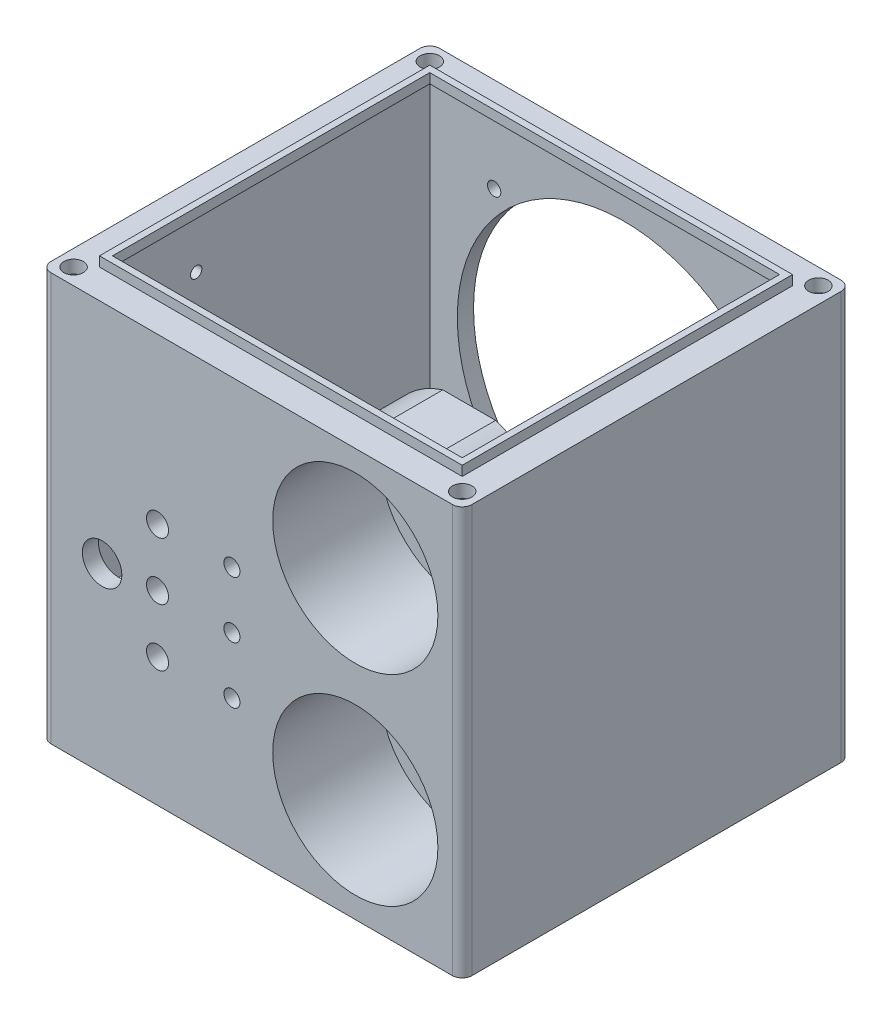
SolidWorks part; units mm, degrees
ref_plane "Front Plane" through (0, 0, 0) normal (0, 0, 1) x (1, 0, 0)
ref_plane "Top Plane" through (0, 0, 0) normal (0, 1, 0) x (1, 0, 0)
ref_plane "Right Plane" through (0, 0, 0) normal (1, 0, 0) x (0, 0, -1)
sketch "Sketch1" plane through (0, 0, 0) normal (0, 0, 1) x (1, 0, 0)
  line L1 (65, -63) -> (-65, -63)
  line L2 (65, -63) -> (65, 63)
  line L3 (65, 63) -> (-65, 63)
  line L4 (-65, -63) -> (-65, 63)
  line L5 (65, -63) -> (-65, 63) construction
  line L6 (65, 63) -> (-65, -63) construction
  point P0 (0, 0)
  dimension "D1" = 126
  dimension "D2" = 130
extrude "Boss-Extrude1" add sketch "Sketch1" along normal blind 120
sketch "Sketch2" plane through (0, 0, 120) normal (0, 0, 1) x (1, 0, 0)
  line L0 (32, 63) -> (32, 31) construction
  line L1 (3.05, -33) -> (-58, -33) construction
  line L2 (3.05, -33) -> (3.05, 21.94) construction
  line L3 (3.05, 21.94) -> (-58, 21.94) construction
  line L4 (-58, -33) -> (-58, 21.94) construction
  line L5 (3.05, -33) -> (-58, 21.94) construction
  line L6 (3.05, 21.94) -> (-58, -33) construction
  line L7 (65, 63) -> (-65, 63) construction
  line L8 (32, 0) -> (32, 31) construction
  line L9 (32, 31) -> (65, 31) construction
  line L10 (65, -63) -> (65, 63) construction
  line L11 (65, 31) -> (32, 0) construction
  line L12 (-47.475, -63) -> (-47.475, -53) construction
  line L13 (-65, -63) -> (65, -63) construction
  line L14 (-47.475, -53) -> (-7.475, -53) construction
  line L15 (-7.475, -53) -> (-7.475, -63) construction
  line L16 (-7.475, -63) -> (-47.475, -63) construction
  line L17 (32, 0) -> (65, 0) construction
  line L18 (-65, 63) -> (-65, -63) construction
  line L19 (-27.475, -5.53) -> (-27.475, -53) construction
  line L20 (-29.08, 12.19) -> (-6.1, 12.19) construction
  line L21 (32, -63.385) -> (65, -63.385) construction
  line L22 (-6.1, 12.19) -> (-6.1, -5.31) construction
  line L23 (32, 63.385) -> (65, 63.385) construction
  line L24 (-6.1, -5.31) -> (-6.1, -22.81) construction
  line L26 (-29.08, -23.31) -> (-29.08, -5.56) construction
  line L27 (-29.08, -5.56) -> (-29.08, 12.19) construction
  line L29 (-46.2, -6.9) -> (-46.2, -5.56) construction
  line L30 (-46.2, -5.56) -> (-29.08, -5.56) construction
  circle A0 centre (32, 31) radius 11
  circle A1 centre (-47.475, -53) radius 6 construction
  circle A2 centre (-7.475, -53) radius 6 construction
  circle A3 centre (32, 49.7) radius 3.55
  circle A4 centre (32, 31) radius 32.385 construction
  circle A5 centre (32, -31) radius 32.385 construction
  circle A6 centre (32, 31) radius 18.7 construction
  circle A7 centre (-46.2, -6.9) radius 6.1
  circle A8 centre (-29.08, -5.56) radius 3.4
  circle A9 centre (-29.08, 12.19) radius 3.4
  circle A10 centre (-29.08, -23.31) radius 3.4
  circle A11 centre (-6.1, -22.81) radius 2.476
  circle A12 centre (-6.1, -5.31) radius 2.476
  circle A13 centre (-6.1, 12.19) radius 2.476
  circle A14 centre (32, -49.7) radius 3.55
  circle A15 centre (32, -31) radius 18.7 construction
  circle A16 centre (32, 12.3) radius 3.55
  circle A17 centre (32, -31) radius 11
  circle A18 centre (32, -12.3) radius 3.55
  circle A19 centre (32, 31) radius 18.465 construction
  circle A20 centre (32, -31) radius 18.465 construction
  point P0 (-27.475, -5.53)
  dimension "D1" = 64.77
  dimension "D2" = 61.05
  dimension "D7" = 12
  dimension "D12" = 22
  dimension "D13" = 7.1
  dimension "D14" = 4.952
  dimension "D15" = 6.8
  dimension "D20" = 12.2
  dimension "D24" = 37.4
  dimension "D9" = 36.93
  dimension "D3" = 54.94
  dimension "D4" = 7
  dimension "D5" = 40
  dimension "D6" = 31
  dimension "D8" = 20
  dimension "D10" = 33
  dimension "D11" = 30
  dimension "D16" = 17.75
  dimension "D17" = 17.5
  dimension "D18" = 1.34
  dimension "D19" = 17.12
  dimension "D21" = 11.8
  dimension "D22" = 22.98
  dimension "D23" = 9.69
sketch "Sketch3" plane through (0, 63, 0) normal (0, 1, 0) x (1, 0, 0)
  line L1 (65, -120) -> (-65, -120) construction
  line L2 (65, -120) -> (65, 0) construction
  line L3 (65, 0) -> (-65, 0) construction
  line L4 (-65, -120) -> (-65, 0) construction
  line L5 (65, -120) -> (-65, 0) construction
  line L6 (65, 0) -> (-65, -120) construction
  line L7 (60, -115) -> (-60, -115)
  line L8 (60, -115) -> (60, -5)
  line L9 (60, -5) -> (-60, -5)
  line L10 (-60, -115) -> (-60, -5)
  line L11 (60, -115) -> (-60, -5) construction
  line L12 (60, -5) -> (-60, -115) construction
  point P0 (0, -60)
  point P6 (0, -60)
  dimension "D1" = 5
  dimension "D2" = 5
extrude "Cut-Extrude3" cut sketch "Sketch3" against normal blind 121
extrude "Cut-Extrude4" cut sketch "Sketch2" against normal up to surface (5 mm away) up to face at (0, 2.5, 115)
sketch "Sketch6" plane through (0, 0, 0) normal (0, 0, -1) x (-1, 0, 0)
  line L0 (0, -1.25) -> (0, -63) construction
  line L1 (0, -1.25) -> (-40.1283, 38.8783) construction
  line L2 (-40.1283, 38.8783) -> (40.1283, 38.8783) construction
  line L3 (40.1283, 38.8783) -> (40.1283, -41.3783) construction
  line L4 (40.1283, -41.3783) -> (-40.1283, -41.3783) construction
  line L5 (-40.1283, -41.3783) -> (-40.1283, 38.8783) construction
  line L7 (65, -63) -> (-65, -63) construction
  line L8 (0, -58) -> (65, -58) construction
  line L9 (65, 63) -> (65, -63) construction
  line L10 (65, -58) -> (0, -1.25) construction
  line L11 (0, -1.25) -> (56.75, -1.25) construction
  line L12 (56.75, -1.25) -> (65, -1.25) construction
  circle A0 centre (0, -1.25) radius 51.5
  circle A1 centre (0, -1.25) radius 56.75 construction
  circle A2 centre (40.1283, -41.3783) radius 2.05
  circle A3 centre (-40.1283, -41.3783) radius 2.05
  circle A4 centre (40.1283, 38.8783) radius 2.05
  circle A5 centre (-40.1283, 38.8783) radius 2.05
  dimension "D2" = 103
  dimension "D3" = 113.5
  dimension "D4" = 4.1
  dimension "D1" = 5
  dimension "D5" = 135
extrude "Cut-Extrude5" cut sketch "Sketch6" against normal up to surface (5 mm away) up to face at (0, 2.5, 5)
sketch "Sketch7" plane through (0, 63, 0) normal (0, 1, 0) x (1, 0, 0)
  line L0 (60, -115) -> (60, -5) construction
  line L1 (-60, -5) -> (60, -5)
  line L2 (-60, -5) -> (-60, -115)
  line L3 (-60, -115) -> (60, -115)
  line L4 (60, -5) -> (60, -115)
  line L5 (-65, -120) -> (-65, 0) construction
  line L6 (54, -109) -> (-54, -109)
  line L7 (54, -109) -> (54, -11)
  line L8 (54, -11) -> (-54, -11)
  line L9 (-54, -109) -> (-54, -11)
  line L10 (54, -109) -> (-54, -11) construction
  line L11 (54, -11) -> (-54, -109) construction
  line L12 (65, 0) -> (-65, 0) construction
  line L13 (-60, -60) -> (60, -60) construction
  line L15 (0, 0) -> (0, -120) construction
  line L16 (65, -120) -> (-65, -120) construction
  point P7 (0, -60)
  dimension "D1" = 11
  dimension "D2" = 11
extrude "Boss-Extrude2" add sketch "Sketch7" against normal blind 6
sketch "Sketch8" plane through (0, 63, 0) normal (0, 1, 0) x (1, 0, 0)
  line L0 (0, -11) -> (0, -109) construction
  line L1 (54, -11) -> (-54, -11) construction
  line L2 (-54, -109) -> (54, -109) construction
  line L3 (-65, -120) -> (-65, 0) construction
  line L4 (54, -109) -> (54, -11) construction
  line L5 (54, -60) -> (0, -60) construction
  line L6 (0, -60) -> (-54, -60) construction
  line L7 (-54, -11) -> (-54, -109) construction
  line L8 (54, -109) -> (-54, -109)
  line L9 (54, -109) -> (54, -11)
  line L10 (54, -11) -> (-54, -11)
  line L11 (-54, -109) -> (-54, -11)
  line L12 (54, -109) -> (-54, -11) construction
  line L13 (54, -11) -> (-54, -109) construction
  line L14 (56, -111) -> (-56, -111)
  line L15 (56, -111) -> (56, -9)
  line L16 (56, -9) -> (-56, -9)
  line L17 (-56, -111) -> (-56, -9)
  line L18 (56, -111) -> (-56, -9) construction
  line L19 (56, -9) -> (-56, -111) construction
  line L20 (65, 0) -> (-65, 0) construction
  dimension "D1" = 9
  dimension "D2" = 9
extrude "Boss-Extrude3" add sketch "Sketch8" along normal blind 3
sketch "Sketch9" plane through (0, 63, 0) normal (0, 1, 0) x (1, 0, 0)
  line L0 (-54, -11) -> (54, -109) construction
  line L1 (60, -115) -> (-60, -115) construction
  line L2 (60, -115) -> (60, -5) construction
  line L3 (60, -5) -> (-60, -5) construction
  line L4 (-60, -115) -> (-60, -5) construction
  line L5 (60, -115) -> (-60, -5) construction
  line L6 (60, -5) -> (-60, -115) construction
  line L7 (65, 0) -> (-65, 0) construction
  line L8 (0, 0) -> (0, -60) construction
  line L9 (-65, -120) -> (-65, 0) construction
  circle A0 centre (-60, -5) radius 3
  circle A1 centre (-60, -115) radius 3
  circle A2 centre (60, -115) radius 3
  circle A3 centre (60, -5) radius 3
  point P0 (0, -60)
  dimension "D3" = 6
  dimension "D1" = 5
  dimension "D2" = 5
extrude "Cut-Extrude6" cut sketch "Sketch9" against normal blind 4
chamfer "Chamfer2" distance 6 angle 45 4 edges at (54, 57, 60) (0, 57, 109) (0, 57, 11) (-54, 57, 60)
sketch "Sketch10" plane through (-65, 0, 0) normal (-1, 0, 0) x (0, 0, 1)
  line L0 (92.695, 63) -> (92.695, -0.77) construction
  line L1 (120, 63) -> (0, 63) construction
  line L2 (120, -63) -> (0, -63) construction
  line L3 (120, -6.991) -> (0, -6.991) construction
  line L4 (101.9705, -47.5325) -> (69.5205, -47.5325)
  line L5 (101.9705, -47.5325) -> (101.9705, -26.9585)
  line L6 (101.9705, -26.9585) -> (69.5205, -26.9585)
  line L7 (69.5205, -47.5325) -> (69.5205, -26.9585)
  line L8 (101.9705, -47.5325) -> (69.5205, -26.9585) construction
  line L9 (101.9705, -26.9585) -> (69.5205, -47.5325) construction
  line L10 (108.25, -49.597) -> (63.241, -49.597) construction
  line L11 (108.25, -49.597) -> (108.25, -24.894) construction
  line L12 (108.25, -24.894) -> (63.241, -24.894) construction
  line L13 (63.241, -49.597) -> (63.241, -24.894) construction
  line L14 (108.25, -49.597) -> (63.241, -24.894) construction
  line L15 (108.25, -24.894) -> (63.241, -49.597) construction
  line L16 (113.241, -55) -> (58.25, -55) construction
  line L17 (113.241, -55) -> (113.241, -19.491) construction
  line L18 (113.241, -19.491) -> (58.25, -19.491) construction
  line L19 (58.25, -55) -> (58.25, -19.491) construction
  line L20 (113.241, -55) -> (58.25, -19.491) construction
  line L21 (113.241, -19.491) -> (58.25, -55) construction
  line L22 (0, 63) -> (0, -63) construction
  line L23 (110, -24.894) -> (120, -24.894) construction
  line L36 (86.345, 24.215) -> (83.195, 24.215)
  line L60 (120, 63) -> (120, -63) construction
  line L61 (102.195, 24.215) -> (99.045, 24.215)
  line L64 (108.25, 19.53) -> (77.14, 19.53) construction
  line L65 (108.25, 19.53) -> (108.25, 42.7) construction
  line L66 (108.25, 42.7) -> (77.14, 42.7) construction
  line L67 (77.14, 19.53) -> (77.14, 42.7) construction
  line L68 (108.25, 19.53) -> (77.14, 42.7) construction
  line L69 (108.25, 42.7) -> (77.14, 19.53) construction
  line L70 (110, 17.78) -> (75.39, 17.78) construction
  line L71 (110, 17.78) -> (110, 44.45) construction
  line L72 (110, 44.45) -> (75.39, 44.45) construction
  line L73 (75.39, 17.78) -> (75.39, 44.45) construction
  line L74 (110, 17.78) -> (75.39, 44.45) construction
  line L75 (110, 44.45) -> (75.39, 17.78) construction
  line L76 (113.025, 15.23) -> (72.365, 15.23) construction
  line L77 (113.025, 15.23) -> (113.025, 47) construction
  line L78 (113.025, 47) -> (72.365, 47) construction
  line L79 (72.365, 15.23) -> (72.365, 47) construction
  line L80 (113.025, 15.23) -> (72.365, 47) construction
  line L81 (113.025, 47) -> (72.365, 15.23) construction
  line L82 (102.195, 24.215) -> (102.195, 38.015)
  line L83 (102.195, 38.015) -> (83.195, 38.015)
  line L84 (83.195, 24.215) -> (83.195, 38.015)
  line L85 (102.195, 24.215) -> (83.195, 38.015) construction
  line L86 (102.195, 38.015) -> (83.195, 24.215) construction
  line L87 (99.045, 21.215) -> (86.345, 21.215)
  line L88 (99.045, 21.215) -> (99.045, 24.215)
  line L90 (86.345, 21.215) -> (86.345, 24.215)
  line L91 (99.045, 21.215) -> (86.345, 24.215) construction
  line L92 (99.045, 24.215) -> (86.345, 21.215) construction
  circle A0 centre (63.241, -24.894) radius 1.75
  circle A1 centre (108.25, -24.894) radius 1.75
  circle A2 centre (108.25, -49.597) radius 1.75
  circle A3 centre (63.241, -49.597) radius 1.75
  circle A12 centre (77.14, 42.7) radius 1.75
  circle A13 centre (108.25, 42.7) radius 1.75
  circle A14 centre (108.25, 19.53) radius 1.75
  circle A15 centre (77.14, 19.53) radius 1.75
  point P1 (0, 0)
  point P6 (85.7455, -37.2455)
  point P11 (85.7455, -37.2455)
  point P16 (85.7455, -37.2455)
  point P29 (92.695, 31.115)
  point P50 (83.3409, 0)
  point P51 (92.695, 31.115)
  point P52 (92.695, 22.715)
  point P62 (0, 0)
  point P63 (82.695, -2.982)
  point P64 (0, 0)
  dimension "D5" = 3.5
  dimension "D13" = 19
  dimension "D11" = 3.5
  dimension "D1" = 45.009
  dimension "D2" = 20.574
  dimension "D3" = 24.703
  dimension "D4" = 32.45
  dimension "D6" = 35.509
  dimension "D7" = 54.991
  dimension "D8" = 8
  dimension "D9" = 12.5
  dimension "D10" = 31.11
  dimension "D12" = 23.17
  dimension "D14" = 13.8
  dimension "D15" = 10
  dimension "D16" = 12.7
  dimension "D17" = 3
  dimension "D18" = 10
  dimension "D19" = 31.77
  dimension "D20" = 40.66
  dimension "D21" = 16
extrude "Cut-Extrude10" cut sketch "Sketch10" against normal blind 10
fillet "Fillet4" radius 3 4 edges at (65, 0, 120) (65, 0, 0) (-65, 0, 0) (-65, 0, 120)
sketch "Sketch16" plane through (0, 0, 120) normal (0, 0, 1) x (1, 0, 0)
  circle A0 centre (32, 31) radius 25.5
  circle A1 centre (32, -31) radius 25.5
  dimension "D1" = 51
extrude "Cut-Extrude9" cut sketch "Sketch16" against normal blind 2
sketch "Sketch17" plane through (0, 0, 115) normal (0, 0, -1) x (-1, 0, 0)
  line L1 (-23.8414, 57) -> (-40.1586, 57)
  line L2 (60, 57) -> (-60, 57) construction
  circle A1 centre (-32, -31) radius 25.25
  circle A2 centre (-32, 31) radius 11
  circle A3 centre (-32, 49.7) radius 3.55 construction
  circle A4 centre (-32, 12.3) radius 3.55 construction
  circle A5 centre (-32, -31) radius 11
  circle A6 centre (-32, -12.3) radius 3.55 construction
  circle A7 centre (-32, -49.7) radius 3.55 construction
  circle A9 centre (-32, 31) radius 25.25
  arc A10 (-40.1586, 57) -> (-23.8414, 57) centre (-32, 31) ccw
  circle A11 centre (-32, 49.7) radius 3.55 construction
  circle A12 centre (-32, 31) radius 11 construction
  circle A13 centre (-32, -31) radius 27.25
  dimension "D1" = 50.5
  dimension "D2" = 2
sketch "Sketch18" plane through (0, 0, 115) normal (0, 0, -1) x (-1, 0, 0)
  line L0 (-40.1586, 57) -> (-23.8414, 57)
  arc A0 (-40.1586, 57) -> (-23.8414, 57) centre (-32, 31) ccw
  circle A1 centre (-32, 31) radius 25.25
  circle A2 centre (-32, -31) radius 25.25
  circle A3 centre (-32, -31) radius 27.25
extrude "Boss-Extrude4" add sketch "Sketch18" along normal blind 28.16
sketch "Sketch19" plane through (0, 0, 86.84) normal (0, 0, -1) x (-1, 0, 0)
  line L0 (-40.1586, 57) -> (-23.8414, 57)
  arc A0 (-40.1586, 57) -> (-23.8414, 57) centre (-32, 31) ccw
  circle A1 centre (-32, -31) radius 27.25
  arc A2 (-28.3173, -58) -> (-35.6827, -58) centre (-32, -31) ccw construction
extrude "Boss-Extrude5" add sketch "Sketch19" along normal blind 2
sketch "Sketch20" plane through (0, 0, 118) normal (0, 0, 1) x (1, 0, 0)
  circle A0 centre (32, 49.7) radius 3.55
  circle A1 centre (32, 31) radius 11
  circle A2 centre (32, 12.3) radius 3.55
  circle A3 centre (32, -31) radius 11
  circle A4 centre (32, -12.3) radius 3.55
  circle A5 centre (32, -49.7) radius 3.55
extrude "Cut-Extrude11" cut sketch "Sketch20" against normal blind 51
sketch "Sketch21" plane through (0, 0, 118) normal (0, 0, 1) x (1, 0, 0)
  circle A0 centre (32, 31) radius 25.5
  circle A1 centre (32, -31) radius 25.5
extrude "Cut-Extrude12" cut sketch "Sketch21" against normal up to surface (31.16 mm away) up to face at (28.45, 49.7, 86.84)
